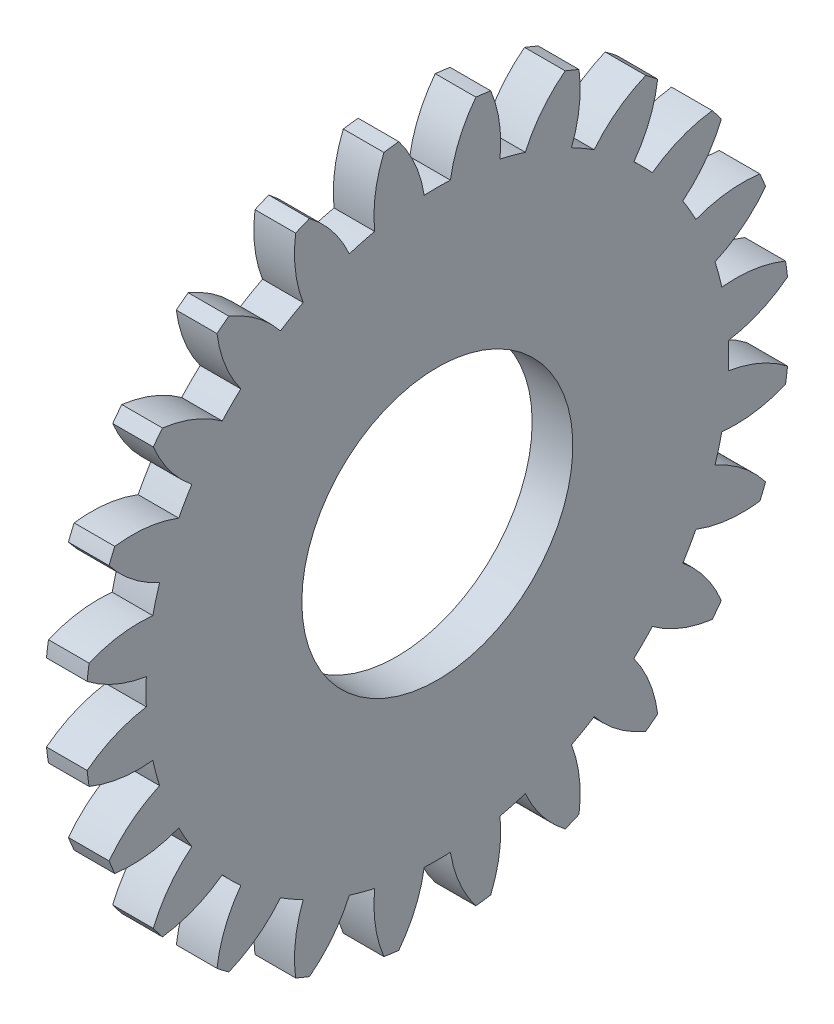
SolidWorks part; units mm, degrees
ref_plane "Plane1" through (0, 0, 0) normal (0, 0, 1) x (1, 0, 0)
ref_plane "Plane2" through (0, 0, 0) normal (0, 1, 0) x (1, 0, 0)
ref_plane "Plane3" through (0, 0, 0) normal (1, 0, 0) x (0, 0, -1)
sketch "HoldingSke" plane through (0, 0, 0) normal (0, 1, 0) x (1, 0, 0)
  line L0 (0, 0) -> (0.9135, -0.4067)
  line L1 (-15, 0) -> (100, 0) construction
  line L2 (0, 0) -> (-2.1039, 2.3779)
  line L3 (0, 0) -> (-11.863, 4.5341)
  line L4 (0, 0) -> (7.8894, 3.5126)
  line L5 (0, 0) -> (-46.8476, -17.4728)
  line L6 (0, 0) -> (-1.2434, -0.839)
  line L7 (-2.1039, 2.3779) -> (8.6586, 51.2059)
  line L8 (-76.2, 54.61) -> (-74.4, 54.61)
  line L9 (-71.009, 38.7566) -> (-53.1078, 45.2721)
  line L10 (-76.2, 71.12) -> (104.1128, 71.12)
  line L11 (0, 0) -> (-1.5, 0)
  line L12 (-76.2, 101.6) -> (-76.162, 101.6)
  line L13 (24.9733, 27.94) -> (52.9518, 28.4284)
  line L14 (24.9733, 27.94) -> (24.9743, 27.94)
  line L15 (24.9733, 27.94) -> (100.4006, 29.5858)
  line L16 (-63.627, -1) -> (-12.827, -1)
  circle A0 centre (0, 0) radius 5
  circle A1 centre (0, 0) radius 10.749
  circle A2 centre (0, 0) radius 37.5
  circle A3 centre (0, 0) radius 5
  dimension "Num_teeth" = 24
  dimension "Pitch_radius" = 180.3128
  dimension "Width" = 1.5
  dimension "Thickness" = 1.5
sketch "BasProSke" plane through (0, 0, 0) normal (0, 1, 0) x (1, 0, 0)
  line L0 (-10, 0) -> (60, 0) construction
  line L1 (0, 0) -> (0, 13)
  line L2 (0, 0) -> (1.5, 0)
  line L3 (1.5, 0) -> (1.5, 13)
  line L4 (1.5, 13) -> (0, 13)
  dimension "Thickness" = 1.5
  dimension "Diameter" = 26
revolve "Base-Revolve" add sketch "BasProSke" angle 360 about L0
sketch "TooCutSke" plane through (0, 0, 0) normal (1, 0, 0) x (0, 0, -1)
  line L1 (0, 0) -> (0, 107) construction
  line L2 (0, 0) -> (-0.8513, 11.9698) construction
  line L3 (0, 0) -> (-3.127, 23.752) construction
  line L4 (-0.8513, 11.9698) -> (-1.5635, 11.876) construction
  arc A0 (0.4834, 10.7381) -> (-0.4834, 10.7381) centre (0, 0) ccw
  arc A1 (1.4409, 12.9455) -> (-1.4409, 12.9455) centre (0, 0) ccw
  circle A2 centre (0, 0) radius 12 construction
  circle A3 centre (0, 0) radius 11.2763 construction
  arc A4 (-0.4834, 10.7381) -> (-1.4409, 12.9455) centre (-5.2252, 9.9926) ccw
  arc A5 (1.4409, 12.9455) -> (0.4834, 10.7381) centre (5.2252, 9.9926) ccw
extrude "ToothCut" cut sketch "TooCutSke" along normal through all
fillet "Breaks" [suppressed] radius 0.02 tangent propagation no
fillet "RootFillets" [suppressed] radius 0.251
pattern_circular "TeethCuts" count 24 every 15 about axis through (-10, 0, 0) along (1, 0, 0) of "ToothCut", "RootFillets", "Breaks"
sketch "HubNeaOneSke" plane through (0, 0, 0) normal (-1, 0, 0) x (0, 0, 1)
  circle A0 centre (0, 0) radius 10.749
  dimension "Diameter" = 21.498
extrude "HubNearOne" [suppressed] add sketch "HubNeaOneSke" along normal blind 48.5001
sketch "HubNeaBotSke" plane through (0, 0, 0) normal (-1, 0, 0) x (0, 0, 1)
  circle A0 centre (0, 0) radius 10.749
  dimension "Diameter" = 21.498
extrude "HubNearBoth" [suppressed] add sketch "HubNeaBotSke" along normal blind 24.25
ref_plane "FarPln" through (1.5, 0, 0) normal (1, 0, 0) x (0, 0, -1)
sketch "HubFarSke" plane through (1.5, 0, 0) normal (1, 0, 0) x (0, 0, -1)
  circle A0 centre (0, 0) radius 10.749
  dimension "Diameter" = 21.498
extrude "HubFar" [suppressed] add sketch "HubFarSke" along normal blind 24.25
sketch "BorSke" plane through (0, 0, 0) normal (1, 0, 0) x (0, 0, -1)
  circle A0 centre (0, 0) radius 5
  dimension "Diameter" = 10
extrude "Bore" cut sketch "BorSke" along normal mid plane 100.0001
sketch "KeySke" plane through (0, 0, 0) normal (1, 0, 0) x (0, 0, -1)
  line L0 (-1.5, 0) -> (-1.5, 6.8)
  line L1 (-1.5, 6.8) -> (1.5, 6.8)
  line L2 (1.5, 6.8) -> (1.5, 0)
  line L3 (0, 0) -> (0, 34) construction
  line L4 (-1.5, 0) -> (1.5, 0)
  dimension "Width" = 3
extrude "Keyway" [suppressed] cut sketch "KeySke" along normal mid plane 100.0001
pattern_circular "Keyway2" [suppressed] count 2 every 90 about axis through (-10, 0, 0) along (1, 0, 0)
equation "' \"Module@HoldingSke\" = 6.35"
equation "' \"Num_teeth@HoldingSke\" = 12"
equation "' \"Ap@HoldingSke\" =  20"
equation "' \"Ap@HoldingSke\" = 20"
equation "' \"Width@HoldingSke\" = 0.5 * 25.4"
equation "' \"Hub_dia@HoldingSke\"= 1 * 25.4"
equation "' \"Hub_dia@HoldingSke\" = 1 * 25.4"
equation "' \"Overall_len@HoldingSke\" = 1.0 * 25.4"
equation "' \"Bore@HoldingSke\" = 0.75 * 25.4"
equation "' \"T_dim@HoldingSke\" = 0.1 * 25.4"
equation "' \"Width@KeySke\" = 0.25 * 25.4"
equation "' \"Show_teeth@HoldingSke\" = 13"
equation "' \"Backlash@HoldingSke\" = 0.009 * 25.4"
equation "' \"Addendum_fac@HoldingSke\" = 1.0"
equation "' \"Dedendum_fac@HoldingSke\" = 1.25"
equation "' \"Dedendum_add@HoldingSke\" = 0.00005 * 25.4"
equation "' \"Clearance_fac@HoldingSke\" = 0.25"
equation "\"Pitch@HoldingSke\" = 1 / \"Module@HoldingSke\""
equation "\"Overcut_dia@TooCutSke\" = (\"Num_teeth@HoldingSke\" + 2 * \"Addendum_fac@HoldingSke\") / \"Pitch@HoldingSke\" + 0.002 * 25.4"
equation "\"Pitch_dia@TooCutSke\" = \"Num_teeth@HoldingSke\" / \"Pitch@HoldingSke\""
equation "\"Base_dia@TooCutSke\" = \"Num_teeth@HoldingSke\" / \"Pitch@HoldingSke\" * cos((\"Ap@HoldingSke\"  * 3.14159265 / 180))"
equation "\"Root_dia@TooCutSke\" = (\"Num_teeth@HoldingSke\" + 2) / \"Pitch@HoldingSke\" - 2 * (\"Addendum_fac@HoldingSke\" + \"Dedendum_fac@HoldingSke\") / \"Pitch@HoldingSke\" - \"Dedendum_add@HoldingSke\" * 2"
equation "\"Half_ang@TooCutSke\" = 180 / \"Num_teeth@HoldingSke\""
equation "\"Half_CT@TooCutSke\" = \"Num_teeth@HoldingSke\" / \"Pitch@HoldingSke\" * sin((3.14159265 / 2 / \"Num_teeth@HoldingSke\")) / 2 - 7 * \"Backlash@HoldingSke\" / 4"
equation "\"Flank_rad@TooCutSke\" = \"Num_teeth@HoldingSke\" / \"Pitch@HoldingSke\" / 5"
equation "\"Radius@RootFillets\" = \"Clearance_fac@HoldingSke\" / \"Pitch@HoldingSke\" + \"Dedendum_add@HoldingSke\""
equation "\"Break_rad@Breaks\" = 0.02 / \"Pitch@HoldingSke\""
equation "\"Thickness@HoldingSke\" = \"Width@HoldingSke\""
equation "\"OAL@HoldingSke\" = \"Thickness@HoldingSke\""
equation "\"MHD@HoldingSke\" = (\"Num_teeth@HoldingSke\" + 2) / \"Pitch@HoldingSke\" - 2 * (\"Addendum_fac@HoldingSke\" + \"Dedendum_fac@HoldingSke\")  / \"Pitch@HoldingSke\" - \"Dedendum_add@HoldingSke\" * 2"
equation "\"MBD@HoldingSke\" = (\"Num_teeth@HoldingSke\" + 2) / \"Pitch@HoldingSke\" - 2 * (\"Addendum_fac@HoldingSke\" + \"Dedendum_fac@HoldingSke\")  / \"Pitch@HoldingSke\" - \"Dedendum_add@HoldingSke\" * 2 - 0.002 * 25.4"
equation "\"MHD@HoldingSke\" = ((sgn( \"MHD@HoldingSke\" - \"Hub_dia@HoldingSke\" )-1)*( \"MHD@HoldingSke\" - \"Hub_dia@HoldingSke\" ))/-2+ \"Hub_dia@HoldingSke\""
equation "\"MBD@HoldingSke\" = ((sgn( \"MBD@HoldingSke\" - \"Bore@HoldingSke\" )-1)*( \"MBD@HoldingSke\" - \"Bore@HoldingSke\" ))/-2+ \"Bore@HoldingSke\""
equation "\"OAL@HoldingSke\" = ((sgn( \"OAL@HoldingSke\" - \"Overall_len@HoldingSke\" )+1)*( \"OAL@HoldingSke\" - \"Overall_len@HoldingSke\" ))/2 + \"Overall_len@HoldingSke\" + 0.000002 * 25.4"
equation "\"Num_teeth@TeethCuts\" = int( \"Show_teeth@HoldingSke\" ) + 1"
equation "\"Num_teeth@TeethCuts\" = ((sgn( \"Num_teeth@TeethCuts\" - \"Num_teeth@HoldingSke\" )-1)*( \"Num_teeth@TeethCuts\" - \"Num_teeth@HoldingSke\" ))/-2+ \"Num_teeth@HoldingSke\""
equation "\"Num_teeth@TeethCuts\" = ((sgn( \"Num_teeth@TeethCuts\" - 2.0)+1)*( \"Num_teeth@TeethCuts\" - 2.0))/2 +2.0"
equation "\"Angle@TeethCuts\" = 360.0 / \"Num_teeth@HoldingSke\""
equation "\"Diameter@BasProSke\" = (\"Num_teeth@HoldingSke\" + 2 * \"Addendum_fac@HoldingSke\") / \"Pitch@HoldingSke\""
equation "\"Thickness@BasProSke\"  = \"Thickness@HoldingSke\""
equation "' \"Fillet_rad@BasProSke\" =  \"Thickness@HoldingSke\" * 0.05"
equation "' \"Fillet_rad@BasProSke\" = \"Thickness@HoldingSke\" * 0.05"
equation "\"MHD@HoldingSke\" = ((sgn( \"MHD@HoldingSke\" - \"Root_dia@TooCutSke\" )-1)*( \"MHD@HoldingSke\" - \"Root_dia@TooCutSke\" ))/-2+ \"Root_dia@TooCutSke\""
equation "\"Diameter@HubNeaOneSke\" = \"MHD@HoldingSke\""
equation "\"Length@HubNearOne\" = \"OAL@HoldingSke\" - \"Thickness@BasProSke\""
equation "\"Diameter@HubNeaBotSke\" = \"MHD@HoldingSke\""
equation "\"Length@HubNearBoth\" = ( \"OAL@HoldingSke\" - \"Thickness@BasProSke\" ) / 2.0"
equation "\"Thickness@FarPln\" = \"Thickness@BasProSke\""
equation "\"Diameter@HubFarSke\" = \"MHD@HoldingSke\""
equation "\"Length@HubFar\" = ( \"OAL@HoldingSke\" - \"Thickness@BasProSke\" ) / 2.0"
equation "\"Diameter@BorSke\" = \"MBD@HoldingSke\""
equation "\"D1@Bore\" = \"OAL@HoldingSke\" * 2.0"
equation "\"D1@Keyway\" = \"OAL@HoldingSke\" * 2.0"
equation "\"Offset@KeySke\" = \"T_dim@HoldingSke\" + \"MBD@HoldingSke\" / 2.0"
